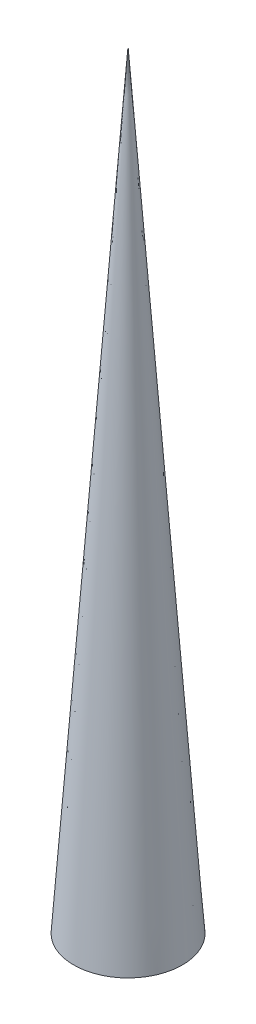
SolidWorks part; units mm, degrees
material "6061-T6 (SS)"
ref_plane "Front Plane" through (0, 0, 0) normal (0, 0, 1) x (1, 0, 0)
ref_plane "Top Plane" through (0, 0, 0) normal (0, 1, 0) x (1, 0, 0)
ref_plane "Right Plane" through (0, 0, 0) normal (1, 0, 0) x (0, 0, -1)
sketch "Sketch2" plane through (0, 0, 0) normal (0, 0, 1) x (1, 0, 0)
  line L0 (0, 0) -> (0, 152.4) construction
  line L1 (0, 0) -> (-10.795, 0)
  line L2 (-10.795, 0) -> (0, 152.4)
  line L3 (0, 152.4) -> (0, 0)
  dimension "D1" = 152.4
  dimension "D2" = 10.795
revolve "Revolve1" add sketch "Sketch2" angle 360 about L0
shell "Shell1" thickness 3.81 removed face at (0, 0, -10.795)
